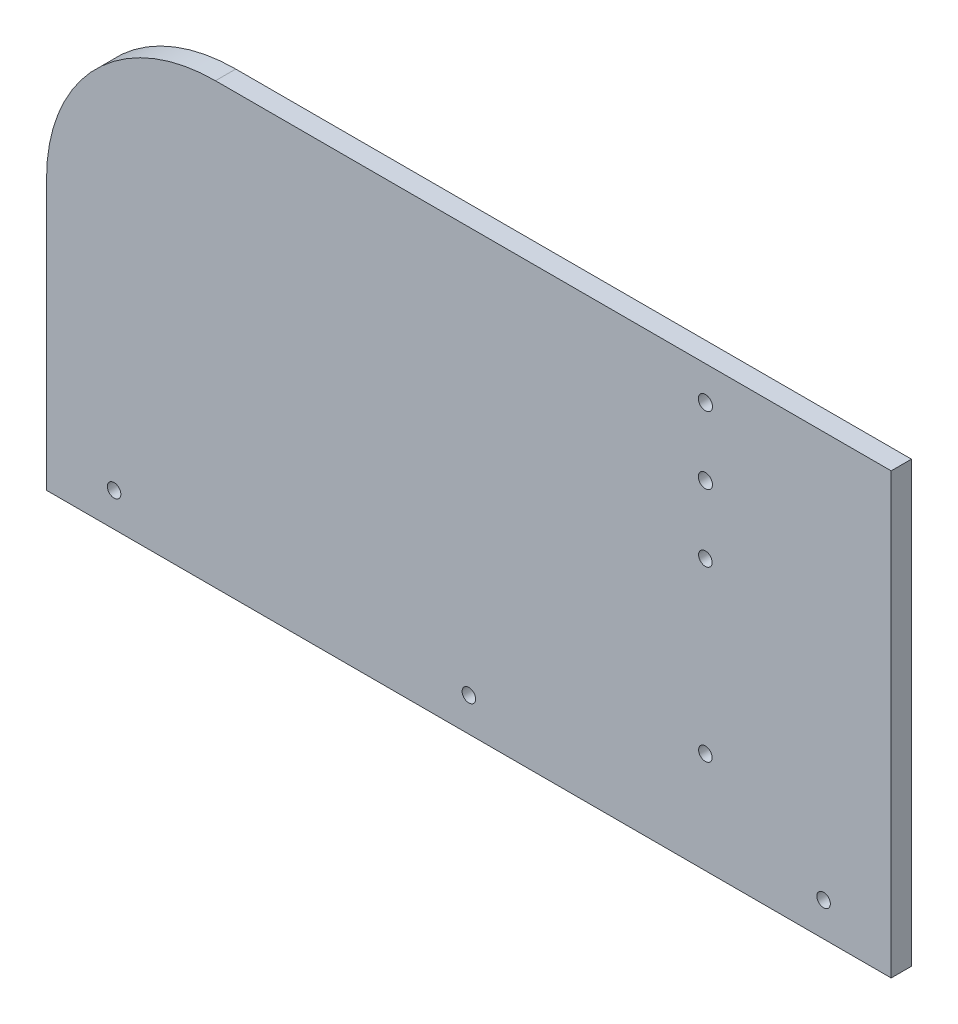
SolidWorks part; units mm, degrees
ref_plane "Plano frontal" through (0, 0, 0) normal (0, 0, 1) x (1, 0, 0)
ref_plane "Plano superior" through (0, 0, 0) normal (0, 1, 0) x (1, 0, 0)
ref_plane "Plano direito" through (0, 0, 0) normal (1, 0, 0) x (0, 0, -1)
sketch "Esboço1" plane through (0, 0, 0) normal (0, 0, 1) x (1, 0, 0)
  line L1 (-125, 65) -> (125, 65)
  line L2 (-125, 65) -> (-125, -65)
  line L3 (-125, -65) -> (125, -65)
  line L4 (125, 65) -> (125, -65)
  line L5 (-125, 65) -> (125, -65) construction
  line L6 (-125, -65) -> (125, 65) construction
  point P0 (0, 0)
  dimension "D1" = 250
  dimension "D2" = 130
extrude "Ressalto-extrusão1" add sketch "Esboço1" along normal blind 6
fillet "Filete1" radius 50 1 edges at (-125, 65, 3)
sketch "Esboço2" plane through (0, 0, 0) normal (0, 0, -1) x (-1, 0, 0)
  line L2 (125, -55) -> (-125, -55)
  line L3 (125, -55) -> (-125, -55) construction
  line L7 (105, 15) -> (105, -65)
  line L8 (105, 15) -> (105, -65) construction
  line L10 (-105, -65) -> (-105, 65)
  line L11 (-105, -65) -> (-105, 65) construction
  circle A0 centre (0, -55) radius 2
  circle A1 centre (105, -55) radius 2
  circle A2 centre (-105, -55) radius 2
  dimension "D4" = 4
  dimension "D1" = 10
  dimension "D2" = 20
  dimension "D3" = 20
extrude "Corte-extrusão1" cut sketch "Esboço2" against normal up to surface (6 mm away) up to face at (-17.0711, 5.0711, 6)
sketch "Esboço3" plane through (0, 0, 0) normal (0, 0, -1) x (-1, 0, 0)
  circle A0 centre (-70, 55) radius 2.1 construction
  circle A1 centre (-70, 35) radius 2.1 construction
  circle A2 centre (-70, 55) radius 2.1
  circle A3 centre (-70, 35) radius 2.1
extrude "Corte-extrusão2" cut sketch "Esboço3" against normal up to surface (6 mm away) up to face at (-103, -55, 6)
sketch "Esboço4" plane through (0, 0, 0) normal (0, 0, -1) x (-1, 0, 0)
  line L0 (-70, 15) -> (-70, -35) construction
  line L1 (-70, -34.55) -> (-70, -55.45) construction
  line L2 (-70, -10) -> (-42.9462, -10) construction
  line L3 (-59, -10) -> (-81, -10) construction
  circle A0 centre (-70, 15) radius 2
  circle A1 centre (-70, -35) radius 2
  dimension "D1" = 4
  dimension "D2" = 50
extrude "Corte-extrusão3" cut sketch "Esboço4" against normal up to surface (6 mm away) up to face at (72.1, 55, 6)
chamfer "Chanfro1" distance 2.3 angle 45 7 edges at (-107, -55, 0) (-2, -55, 0) (103, -55, 0) (68, -35, 0) (68, 15, 0) (67.9, 35, 0) (67.9, 55, 0)
ref_axis "Eixo1" through (70, 15, 6) along (0, 0, -1)
ref_axis "Eixo2" through (70, -35, 6) along (0, 0, -1)
ref_plane "Plano1" through (0, -35, 0) normal (0, -1, 0) x (-1, 0, 0)
ref_plane "Plano2" through (0, 15, 0) normal (0, -1, 0) x (-1, 0, 0)
